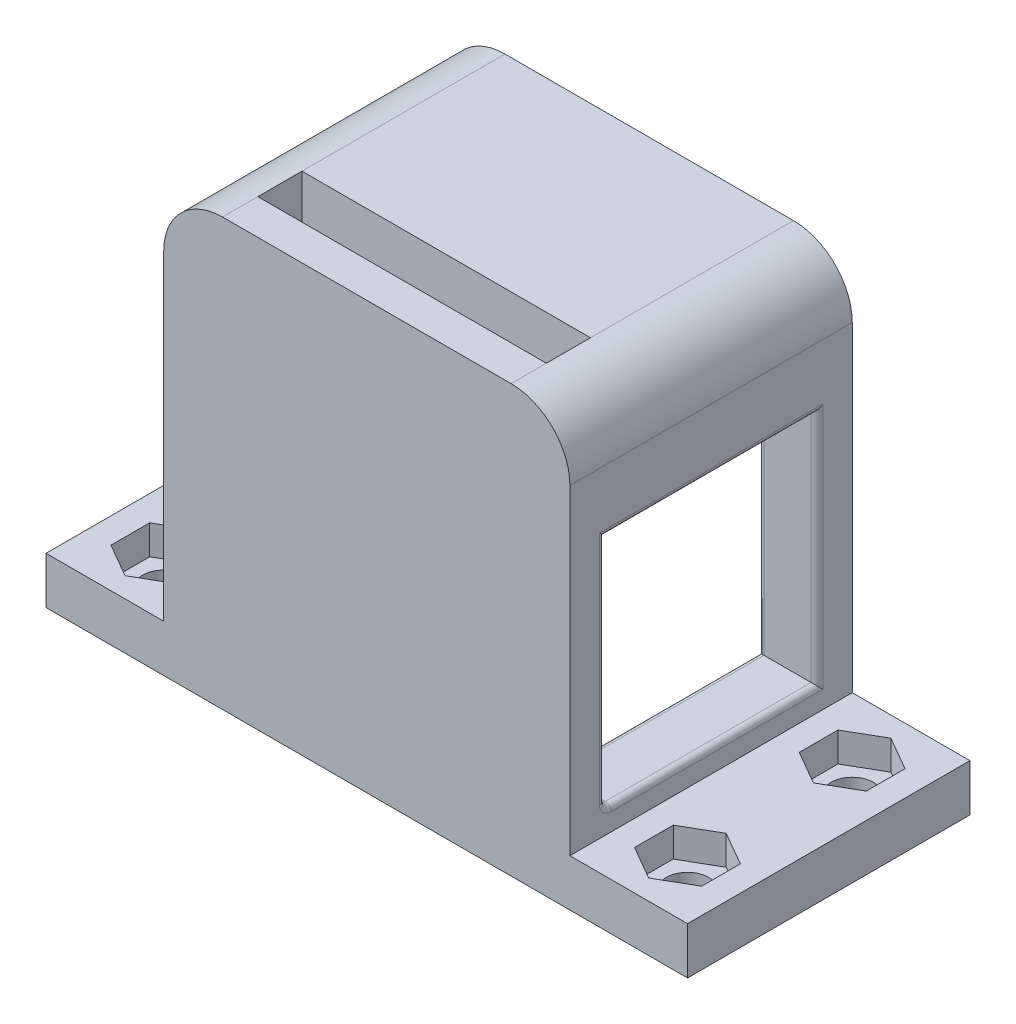
SolidWorks part; units mm, degrees
ref_plane "Front Plane" through (0, 0, 0) normal (0, 0, 1) x (1, 0, 0)
ref_plane "Top Plane" through (0, 0, 0) normal (0, 1, 0) x (1, 0, 0)
ref_plane "Right Plane" through (0, 0, 0) normal (1, 0, 0) x (0, 0, -1)
sketch "Sketch1" plane through (0, 0, 0) normal (0, 0, 1) x (1, 0, 0)
  line L1 (-27.2601, 4.8) -> (-12.2601, 4.8)
  line L2 (-27.2601, 4.8) -> (-27.2601, 8.8)
  line L3 (-27.2601, 8.8) -> (-17.2601, 8.8)
  line L6 (-12.2601, 4.8) -> (-12.2601, 36.5)
  line L8 (-17.2601, 8.8) -> (-17.2601, 39.5587)
  line L9 (-12, 41.05) -> (12, 41.05)
  line L11 (-12.2601, 36.5) -> (12.2601, 36.5)
  line L14 (17.2601, 8.8) -> (17.2601, 38.3587)
  line L15 (12, 41.05) -> (15.1507, 41.05)
  line L16 (12.2601, 4.8) -> (12.2601, 36.5)
  line L18 (27.2601, 8.8) -> (17.2601, 8.8)
  line L19 (27.2601, 4.8) -> (27.2601, 8.8)
  line L20 (27.2601, 4.8) -> (12.2601, 4.8)
  line L21 (-17.2601, 39.5587) -> (-17.2601, 41.05)
  line L22 (-17.2601, 41.05) -> (-12, 41.05)
  line L23 (15.1507, 41.05) -> (17.2601, 41.05)
  line L25 (17.2601, 41.05) -> (17.2601, 38.3587)
  point P4 (0, 36.5)
  dimension "D2" = 5
  dimension "D3" = 10
  dimension "D6" = 4.55
  dimension "D8" = 24.5203
  dimension "D9" = 31.7
  dimension "D10" = 4
  dimension "D11" = 4
extrude "Boss-Extrude1" add sketch "Sketch1" along normal blind 17.5
sketch "Sketch2" plane through (0, 0, 17.5) normal (0, 0, 1) x (1, 0, 0)
  line L0 (-17.2601, 8.8) -> (-17.2601, 41.05)
  line L1 (-17.2601, 41.05) -> (17.2601, 41.05)
  line L2 (17.2601, 41.05) -> (17.2601, 4.8)
  line L3 (12.2601, 4.8) -> (27.2601, 4.8) construction
  line L4 (17.2601, 4.8) -> (-17.2601, 4.8)
  line L5 (-27.2601, 4.8) -> (-12.2601, 4.8) construction
  line L6 (-17.2601, 4.8) -> (-17.2601, 8.8)
extrude "Boss-Extrude2" add sketch "Sketch2" along normal blind 6.5
sketch "Sketch4" plane through (0, 0, 17.5) normal (0, 0, -1) x (-1, 0, 0)
  line L1 (-12.2601, 36.5) -> (12.2601, 36.5)
  line L2 (-12.2601, 36.5) -> (-12.2601, 4.8)
  line L3 (-12.2601, 4.8) -> (12.2601, 4.8)
  line L4 (12.2601, 36.5) -> (12.2601, 4.8)
extrude "Cut-Extrude1" cut sketch "Sketch4" against normal blind 3.5
sketch "Sketch5" plane through (0, 0, 21) normal (0, 0, -1) x (-1, 0, 0)
  line L0 (-17.2601, 41.05) -> (17.2601, 41.05) construction
  line L1 (-12.2601, 36.5) -> (-14.9466, 36.5)
  line L2 (-12.2601, 36.5) -> (-12.2601, 38.5)
  line L3 (-12.2601, 38.5) -> (-14.9466, 38.5)
  line L4 (-14.9466, 36.5) -> (-14.9466, 38.5)
  dimension "D1" = 2.55
extrude "Cut-Extrude2" [suppressed] cut sketch "Sketch5" along normal blind 4.5
fillet "Fillet1" radius 5 2 edges at (-17.2601, 41.05, 12) (17.2601, 41.05, 12)
sketch "Sketch7" plane through (0, 0, 17.5) normal (0, 0, 1) x (1, 0, 0)
  line L1 (-27.2601, 8.8) -> (-17.2601, 8.8)
  line L2 (-27.2601, 8.8) -> (-27.2601, 4.8)
  line L3 (-27.2601, 4.8) -> (-17.2601, 4.8)
  line L4 (-17.2601, 8.8) -> (-17.2601, 4.8)
  line L5 (17.2601, 8.8) -> (27.2601, 8.8)
  line L6 (17.2601, 8.8) -> (17.2601, 4.8)
  line L7 (17.2601, 4.8) -> (27.2601, 4.8)
  line L8 (27.2601, 8.8) -> (27.2601, 4.8)
extrude "Boss-Extrude3" add sketch "Sketch7" along normal through all
sketch "Sketch6" plane through (0, 8.8, 0) normal (0, 1, 0) x (1, 0, 0)
  line L0 (27.2601, -24) -> (27.2601, 0) construction
  line L40 (22.25, -1.7091) -> (25.1, -3.3546)
  line L45 (92.1046, -12) -> (-37.5844, -12) construction
  line L47 (19.4, -3.3546) -> (22.25, -1.7091)
  line L48 (19.4, -6.6454) -> (19.4, -3.3546)
  line L49 (22.25, -8.2909) -> (19.4, -6.6454)
  line L56 (25.1, -6.6454) -> (22.25, -8.2909)
  line L65 (25.1, -3.3546) -> (25.1, -6.6454)
  line L66 (22.25, -22.2909) -> (25.1, -20.6454)
  line L67 (25.1, -20.6454) -> (25.1, -17.3546)
  line L68 (25.1, -17.3546) -> (22.25, -15.7091)
  line L69 (22.25, -15.7091) -> (19.4, -17.3546)
  line L70 (19.4, -17.3546) -> (19.4, -20.6454)
  line L71 (19.4, -20.6454) -> (22.25, -22.2909)
  line L72 (0, -59.0369) -> (0, -80.7994) construction
  line L74 (0, -13.2) -> (0, 13.2) construction
  line L75 (-22.25, -8.2909) -> (-19.4, -6.6454)
  line L76 (-19.4, -6.6454) -> (-19.4, -3.3546)
  line L77 (-19.4, -3.3546) -> (-22.25, -1.7091)
  line L78 (-22.25, -1.7091) -> (-25.1, -3.3546)
  line L79 (-25.1, -3.3546) -> (-25.1, -6.6454)
  line L80 (-25.1, -6.6454) -> (-22.25, -8.2909)
  line L81 (-22.25, -15.7091) -> (-19.4, -17.3546)
  line L82 (-19.4, -17.3546) -> (-19.4, -20.6454)
  line L83 (-19.4, -20.6454) -> (-22.25, -22.2909)
  line L84 (-22.25, -22.2909) -> (-25.1, -20.6454)
  line L85 (-25.1, -20.6454) -> (-25.1, -17.3546)
  line L86 (-25.1, -17.3546) -> (-22.25, -15.7091)
  circle A4 centre (22.25, -19) radius 2.85 construction
  point P4 (27.2601, -12)
  point P12 (20.825, -16.5318)
  point P34 (-20.825, -16.5318)
  dimension "D1" = 22.25
  dimension "D4" = 5.7
  dimension "D2" = 7
fillet "Fillet2" radius 1 2 edges at (12.2601, 20.65, 0) (-12.2601, 20.65, 0)
sketch "Sketch8" plane through (-17.2601, 0, 0) normal (-1, 0, 0) x (0, 0, 1)
  line L0 (24, 36.05) -> (24, 8.8) construction
  line L1 (3, 30.8) -> (21, 30.8)
  line L2 (3, 30.8) -> (3, 10.8)
  line L3 (3, 10.8) -> (21, 10.8)
  line L4 (21, 30.8) -> (21, 10.8)
  line L6 (24, 8.8) -> (0, 8.8) construction
  dimension "D1" = 18
  dimension "D2" = 20
  dimension "D3" = 3
  dimension "D4" = 2
extrude "Cut-Extrude4" cut sketch "Sketch8" against normal through all
fillet "Fillet3" radius 0.5 16 edges at (-14.7601, 10.8, 21) (-17.2601, 10.8, 12) (-17.2601, 20.8, 3) (-17.2601, 20.8, 21) (-17.2601, 30.8, 12) (-12.2601, 10.8, 12) (-12.2601, 20.8, 3) (-12.2601, 7.8, 21) (12.2601, 7.8, 21) (17.2601, 10.8, 12) (12.2601, 20.8, 3) (12.2601, 10.8, 12) (17.2601, 30.8, 12) (17.2601, 20.8, 3) (17.2601, 20.8, 21) (14.7601, 10.8, 21)
extrude "Cut-Extrude7" cut sketch "Sketch6" against normal offset from surface (2.5 mm away) 1.5 up to face at (0, 4.8, 11.0661)
sketch "Sketch11" plane through (0, 8.8, 0) normal (0, 1, 0) x (1, 0, 0)
  line L0 (22.25, -22.2909) -> (25.1, -20.6454) construction
  line L1 (25.1, -17.3546) -> (22.25, -15.7091) construction
  line L2 (19.4, -17.3546) -> (19.4, -20.6454) construction
  line L3 (22.25, -8.2909) -> (25.1, -6.6454) construction
  line L4 (25.1, -3.3546) -> (22.25, -1.7091) construction
  line L5 (19.4, -3.3546) -> (19.4, -6.6454) construction
  line L6 (-22.25, -22.2909) -> (-19.4, -20.6454) construction
  line L7 (-25.1, -17.3546) -> (-25.1, -20.6454) construction
  line L8 (-19.4, -17.3546) -> (-22.25, -15.7091) construction
  line L9 (-22.25, -8.2909) -> (-19.4, -6.6454) construction
  line L10 (-19.4, -3.3546) -> (-22.25, -1.7091) construction
  line L11 (-25.1, -3.3546) -> (-25.1, -6.6454) construction
  circle A0 centre (22.25, -19) radius 2.85
  circle A1 centre (22.25, -5) radius 2.85
  circle A2 centre (-22.25, -5) radius 2.85
  circle A3 centre (-22.25, -19) radius 2.85
hole_wizard "M3 Clearance Hole1" positions "Sketch12" profile "Sketch13" hole size "M3" standard "ANSI Metric" end condition through all
sketch "Sketch12" plane through (0, 8.8, 0) normal (0, 1, 0) x (1, 0, 0)
  point P0 (22.25, -19)
  point P3 (22.25, -5)
  point P6 (-22.25, -5)
  point P9 (-22.25, -19)
sketch "Sketch13" plane through (22.25, 8.8, 19) normal (1, 0, 0) x (0, 0, 1)
  line L0 (0, 0) -> (0, 4)
  line L1 (0, 4) -> (1.8, 4)
  line L2 (1.8, 4) -> (1.8, 0)
  line L5 (1.8, 0) -> (0, 0)
  line L11 (0, -6.35) -> (0, 107.95) construction
  dimension "Thru Hole Dia." = 3.6
  dimension "Thru Hole Depth" = 4
sketch "Sketch14" plane through (0, 36.5, 0) normal (0, -1, 0) x (1, 0, 0)
  line L0 (-12.2601, 21) -> (12.2601, 21) construction
  line L1 (12.2601, 17.25) -> (-12.2601, 17.25)
  line L2 (12.2601, 17.25) -> (12.2601, 21)
  line L3 (12.2601, 21) -> (-12.2601, 21)
  line L4 (-12.2601, 17.25) -> (-12.2601, 21)
  line L5 (-12.2601, 21) -> (-12.2601, 1) construction
  line L6 (12.2601, 21) -> (12.2601, 1) construction
  dimension "D1" = 3.75
extrude "Cut-Extrude8" cut sketch "Sketch14" against normal through all
